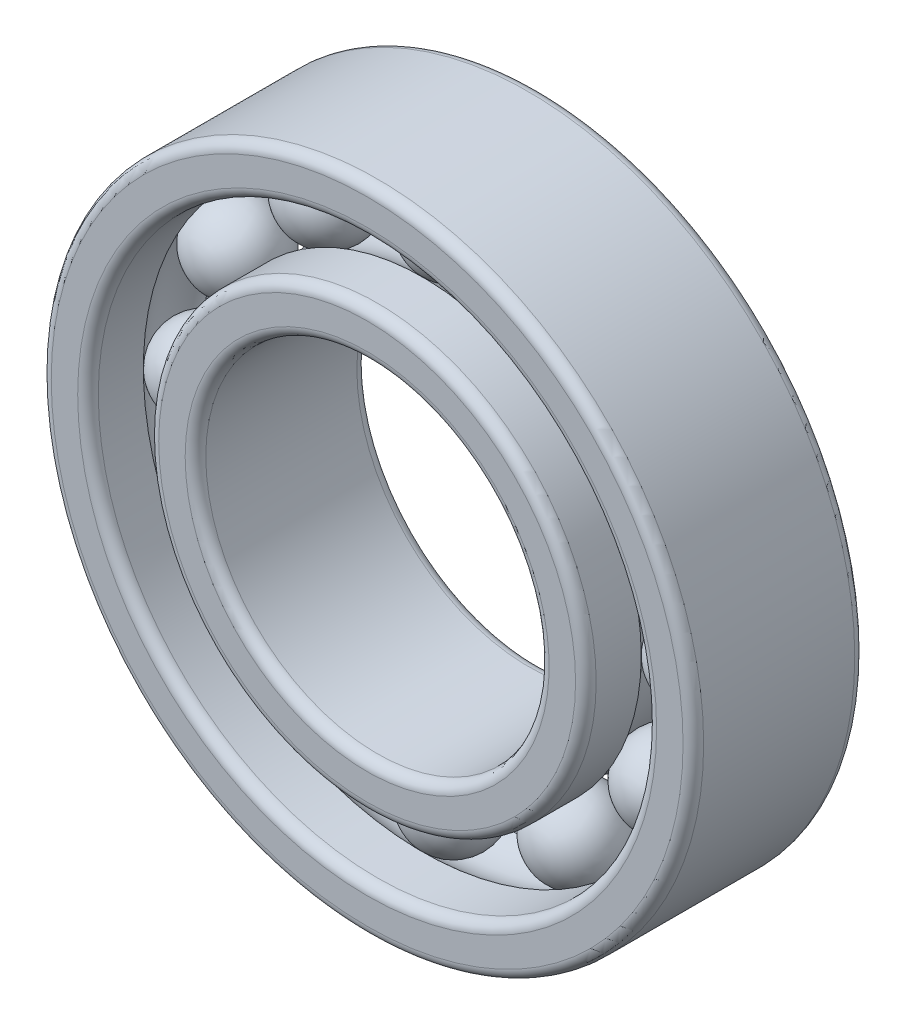
SolidWorks part; units mm, degrees
material "Legierter Stahl"
ref_plane "Ebene vorne" through (0, 0, 0) normal (0, 0, 1) x (1, 0, 0)
ref_plane "Ebene oben" through (0, 0, 0) normal (0, 1, 0) x (1, 0, 0)
ref_plane "Ebene rechts" through (0, 0, 0) normal (1, 0, 0) x (0, 0, -1)
sketch "Skizze1" plane through (0, 0, 0) normal (1, 0, 0) x (0, 0, -1)
  line L0 (0, 0) -> (32.8284, 0) construction
  line L1 (0, 0) -> (0, 22.1569) construction
  line L2 (-2.5, 9.5) -> (2.5, 9.5)
  line L3 (2.5, 9.5) -> (2.5, 8.13)
  line L4 (2.5, 8.13) -> (0.8877, 8.13)
  line L5 (0.8877, 6.37) -> (2.5, 6.37)
  line L6 (2.5, 6.37) -> (2.5, 5)
  line L7 (2.5, 5) -> (-2.5, 5)
  line L8 (-2.5, 6.37) -> (-2.5, 5)
  line L9 (-0.8877, 6.37) -> (-2.5, 6.37)
  line L10 (-2.5, 8.13) -> (-0.8877, 8.13)
  line L11 (-2.5, 9.5) -> (-2.5, 8.13)
  line L12 (-0.8877, 8.13) -> (0, 7.25) construction
  line L13 (0, 7.25) -> (0.8877, 6.37) construction
  line L14 (-1.25, 7.25) -> (1.25, 7.25)
  circle A0 centre (0, 7.25) radius 1.25
  point P17 (0, 5)
  point P22 (0, 9.5)
  dimension "D1" = 10
  dimension "D6" = 2.5
  dimension "D2" = 19
  dimension "D3" = 5
  dimension "D4" = 12.74
  dimension "D5" = 16.26
revolve "Rotation1" add sketch "Skizze1" angle 360 about L0 region at (0, 8.8529, 0) region at (0, 5.6471, 0)
revolve "Rotation3" add sketch "Skizze1<5>" angle 360 about L14 region at (0, 7.7805, 0)
sketch "Skizze1<5>" plane through (0, 0, 0) normal (1, 0, 0) x (0, 0, -1) same geometry as "Skizze1"
ref_axis "Achse1" through (0, 0, -2.5) along (0, 0, 1)
pattern_circular "Kreismuster4" count 12 over 360 about axis through (0, 0, -2.5) along (0, 0, 1) of bodies 110
fillet "Verrundung1" radius 0.3 4 edges at (8.13, 0, -2.5) (8.13, 0, 2.5) (9.5, 0, -2.5) (9.5, 0, 2.5)
fillet "Verrundung2" radius 0.3 4 edges at (6.37, 0, -2.5) (5, 0, -2.5) (6.37, 0, 2.5) (5, 0, 2.5)
